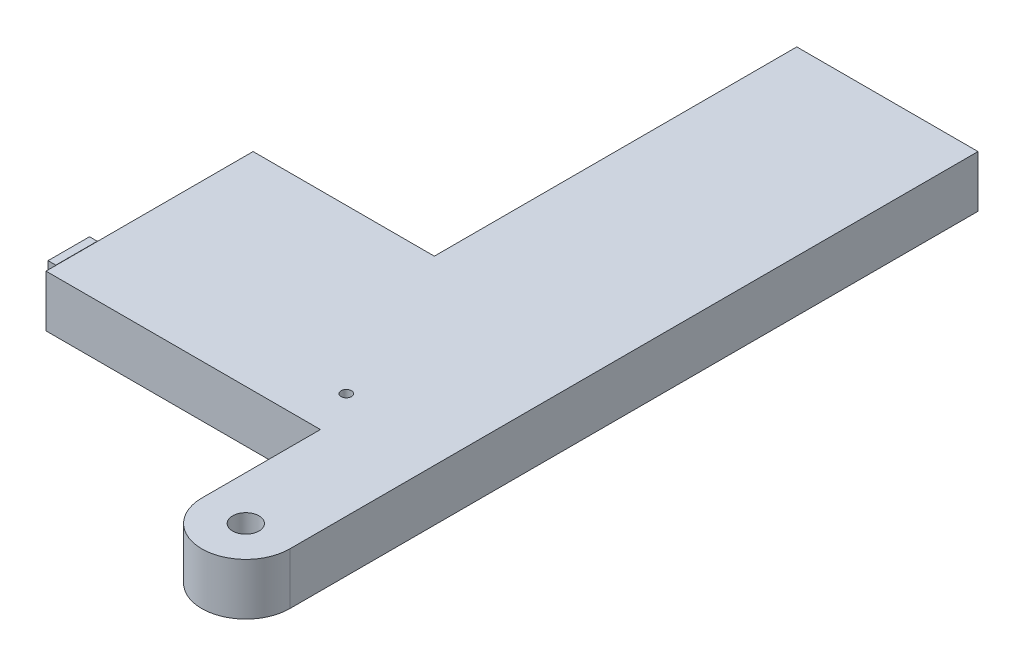
SolidWorks part; units mm, degrees
ref_plane "Front Plane" through (0, 0, 0) normal (0, 0, 1) x (1, 0, 0)
ref_plane "Top Plane" through (0, 0, 0) normal (0, 1, 0) x (1, 0, 0)
ref_plane "Right Plane" through (0, 0, 0) normal (1, 0, 0) x (0, 0, -1)
sketch "CornerrSketch1" plane through (0, 0, 0) normal (0, 1, 0) x (1, 0, 0)
  line L0 (0, 0) -> (0, 80)
  line L5 (0, 80) -> (70, 80)
  line L6 (70, 80) -> (70, 220)
  line L7 (140, 220) -> (70, 220)
  line L8 (106, -45.825) -> (106, 0)
  line L9 (0, 0) -> (106, 0)
  line L10 (140, 220) -> (140, -45.825)
  arc A0 (106, -45.825) -> (140, -45.825) centre (123, -45.825) ccw
  dimension "D5" = 34
  dimension "D4" = 80
  dimension "D3" = 70
  dimension "D1" = 220
  dimension "D2" = 45.825
  dimension "D6" = 140
extrude "CornerBoss-Extrude1" add sketch "CornerrSketch1" along normal blind 20
shell "Shell1" thickness 3 removed face at (79, 0, -61.4188)
sketch "PadSketch1" plane through (0, 17, 0) normal (0, -1, 0) x (1, 0, 0)
  line L1 (0, 0) -> (106, 0) construction
  line L2 (140, 45.825) -> (140, -220) construction
  circle A0 centre (99, -17) radius 5
  circle A1 centre (123, 45.825) radius 12
  dimension "D1" = 10
  dimension "D4" = 24
  dimension "D3" = 17
  dimension "D2" = 41
extrude "PadBoss-Extrude1" add sketch "PadSketch1" along normal blind 10
sketch "StepperShaftCut-Sketch3" plane through (0, 7, 0) normal (0, -1, 0) x (1, 0, 0)
  circle A0 centre (123, 45.825) radius 5.1
  circle A1 centre (99, -17) radius 2
  dimension "D1" = 10.2
  dimension "D2" = 4
extrude "StepperShaftCut-Extrude1" cut sketch "StepperShaftCut-Sketch3" against normal through all
sketch "ThreadedNutMountHolesSketch5" plane through (0, 7, 0) normal (0, -1, 0) x (1, 0, 0)
  circle A0 centre (123, 53.825) radius 2
  circle A1 centre (131, 45.825) radius 2
  circle A2 centre (115, 45.825) radius 2
  circle A3 centre (123, 37.825) radius 2
  dimension "D3" = 4
  dimension "D1" = 8
  dimension "D2" = 16
  dimension "D4" = 8
  dimension "D5" = 16
extrude "ThreadedNutMountHolesCut-Extrude2" cut sketch "ThreadedNutMountHolesSketch5" against normal blind 10
sketch "TopPegHoleSketch4" plane through (0, 0, -220) normal (0, 0, -1) x (-1, 0, 0)
  line L1 (-130, 14) -> (-120, 14)
  line L2 (-130, 14) -> (-130, 0)
  line L3 (-130, 0) -> (-120, 0)
  line L4 (-120, 14) -> (-120, 0)
  line L5 (-140, 0) -> (-70, 0) construction
  line L6 (-140, 20) -> (-140, 0) construction
  dimension "D2" = 10
  dimension "D3" = 14
  dimension "D1" = 10
extrude "TopPegHoleCut-Extrude2" cut sketch "TopPegHoleSketch4" against normal blind 3
sketch "BLPegSketch5" plane through (0, 0, 0) normal (-1, 0, 0) x (0, 0, 1)
  line L1 (-19.9, 13.9) -> (-10.1, 13.9)
  line L2 (-19.9, 13.9) -> (-19.9, 0)
  line L3 (-19.9, 0) -> (-10.1, 0)
  line L4 (-10.1, 13.9) -> (-10.1, 0)
  line L5 (-80, 0) -> (0, 0) construction
  line L6 (0, 20) -> (0, 0) construction
  dimension "D2" = 13.9
  dimension "D3" = 9.8
  dimension "D1" = 10.1
extrude "BLPegBoss-Extrude3" add sketch "BLPegSketch5" along normal blind 3.1
sketch "BLPegCapSketch6" plane through (-3.1, 0, 0) normal (-1, 0, 0) x (0, 0, 1)
  line L0 (-19.9, 13.9) -> (-19.9, 0) construction
  line L1 (-22.9, 17) -> (-6.9, 17)
  line L2 (-22.9, 17) -> (-22.9, 0)
  line L3 (-22.9, 0) -> (-6.9, 0)
  line L4 (-6.9, 17) -> (-6.9, 0)
  line L8 (-19.9, 0) -> (-10.1, 0) construction
  dimension "D1" = 16
  dimension "D3" = 17
  dimension "D2" = 3
extrude "BLPegCapBoss-Extrude4" add sketch "BLPegCapSketch6" along normal blind 3
sketch "BedCenterPegHoleCutSketch1" plane through (70, 0, 0) normal (-1, 0, 0) x (0, 0, 1)
  line L0 (-220, 0) -> (-80, 0) construction
  line L1 (-190, 14) -> (-180, 14)
  line L2 (-190, 14) -> (-190, 0)
  line L3 (-190, 0) -> (-180, 0)
  line L4 (-180, 14) -> (-180, 0)
  line L5 (-80, 20) -> (-80, 0) construction
  dimension "D2" = 10
  dimension "D1" = 14
  dimension "D3" = 100
extrude "BedCenterPegHoleCut-Extrude1" cut sketch "BedCenterPegHoleCutSketch1" against normal blind 3
equation "\"BedThickness\"= 20mm"
equation "\"BedToBuildPlateStandoffHolesDistanceFromLeftOrRight\"= \"BuildPlateStandoffHolesDistanceFromLeftOrRight\" + \"BedIncreasedByWidth\" / 2'Equals 17"
equation "\"BedLLongSide\"= \"BedThirdSize\" * 3'Equals 210"
equation "\"BedLShortSide\"= \"BedThirdSize\" * 2'Equals 140"
equation "\"BedLWidth\"= \"BedThirdSize\"'Equals 70"
equation "\"D4@CornerrSketch1\"=\"BedLWidth\" + \"BedIncreasedByWidth\"/2"
equation "\"BedIncreasedByWidth\"= 20mm"
equation "\"BedIncreasedByLength\"= 0mm"
equation "\"BedThirdSize\"= 70mm"
equation "\"StandardWallThickness\"= 3mm"
equation "\"D2@TopPegHoleSketch4\"=\"BedPegHoleWidth\""
equation "\"D3@TopPegHoleSketch4\"=\"BedPegHoleHeight\""
equation "\"D1@TopPegHoleCut-Extrude2\" = \"StandardWallThickness\""
equation "\"D3@BLPegSketch5\"=\"BedPegWidth\""
equation "\"D1@BLPegBoss-Extrude3\"=\"BedPegBoss\""
equation "\"D2@BLPegSketch5\"=\"BedPegHeight\""
equation "\"D2@BLPegCapSketch6\"=\"StandardWallThickness\""
equation "\"D3@BLPegCapSketch6\"=\"BedPegCapHeight\""
equation "\"D1@BLPegCapBoss-Extrude4\" = \"StandardWallThickness\""
equation "\"D3@CornerrSketch1\"=\"BedLWidth\" "
equation "\"D1@PadSketch1\" = \"BedToBuildPlateStandoffPadSize\""
equation "\"D1@PadBoss-Extrude1\"=\"LeadScrewNutPadDepth\""
equation "\"BedToBuildPlateStandoffPadSize\"= 10mm"
equation "\"BedToBuildPlateStandoffHolesDistanceFromBack\"= \"BuildPlateStandoffHolesDistanceFromBack\" + \"BedIncreasedByLength\" / 2'Equals 41"
equation "\"BuildPlateStandoffHolesDistanceFromLeftOrRight\"= 7mm"
equation "\"BuildPlateStandoffHolesDistanceFromBack\"= 41mm"
equation "\"DistanceFromBedSideToStepperHole\"= ( \"DistanceBetweenLeftToRightStepperHoles\" - \"BedWidth\" ) / 2'Equals 45.825"
equation "\"DistanceBetweenLeftToRightStepperHoles\"= \"FrontBackRailLength\" - \"StepperMountingHoleOffsetFromLeftOrRightSide\" * 2 - \"StepperMountingHoleDistance\"'Equals 461.65"
equation "\"FrontBackRailLength\"= 510mm"
equation "\"StepperMountingHoleOffsetFromLeftOrRightSide\"= \"StepperMountingHoleOffsetFromItsSide\" + \"RailThickness\""
equation "\"StepperMountingHoleDistance\"= 31mm'Spec"
equation "\"StepperMountingHoleOffsetFromItsSide\"= 5.5mm'Spec"
equation "\"RailThickness\"= .125in'Spec"
equation "\"BedWidth\"= \"BedInnerSquareWidth\" + \"BedLWidth\" * 2 + \"BedIncreasedByWidth\"'Equals 370"
equation "\"BedInnerSquareWidth\"= \"BedThirdSize\" * 3'Equals 210"
equation "\"D1@CornerrSketch1\"=\"BedLLongSide\"  + \"BedIncreasedByWidth\"/2"
equation "\"D2@CornerrSketch1\"=\"DistanceFromBedSideToStepperHole\""
equation "\"D3@PadSketch1\"=\"BedToBuildPlateStandoffHolesDistanceFromLeftOrRight\""
equation "\"D2@PadSketch1\"=\"BedToBuildPlateStandoffHolesDistanceFromBack\""
equation "\"D1@TopPegHoleSketch4\"=\"BedTopPegOffsetFromSide\""
equation "\"D1@BLPegSketch5\"=\"BedTopPegOffsetFromSide\" + .1mm"
equation "\"D6@CornerrSketch1\"=\"BedLShortSide\" + \"BedIncreasedByLength\"/2"
equation "\"LeadScrewNutPadSize\"= \"LeadScrewNutMountingHoleFlangeDiameter\" + 2mm'Equals 24"
equation "\"D4@PadSketch1\"=\"LeadScrewNutPadSize\""
equation "\"D1@StepperShaftCut-Sketch3\"=\"LeadScrewNutInnerShaftFlangeDiameter\""
equation "\"D2@StepperShaftCut-Sketch3\"=\"M3HeatInsertHoleDiameter\""
equation "\"LeadScrewNutInnerShaftFlangeDiameter\"= 10.2mm'Spec"
equation "\"LeadScrewNutMountHoleDiameter\"= \"M3HeatInsertHoleDiameter\""
equation "\"LeadScrewNutMountingHoleFlangeDiameter\"= 22mm'Spec"
equation "\"LeadScrewNutMountingHoleDistance\"= 16mm'Spec"
equation "\"D1@ThreadedNutMountHolesSketch5\"=\"LeadScrewNutMountingHoleDistance\"/2"
equation "\"D2@ThreadedNutMountHolesSketch5\"=\"LeadScrewNutMountingHoleDistance\""
equation "\"D4@ThreadedNutMountHolesSketch5\"=\"LeadScrewNutMountingHoleDistance\"/2"
equation "\"D5@ThreadedNutMountHolesSketch5\"=\"LeadScrewNutMountingHoleDistance\""
equation "\"D3@ThreadedNutMountHolesSketch5\"=\"LeadScrewNutMountHoleDiameter\""
equation "\"LeadScrewNutPadDepth\"= \"BedThickness\" / 2'Equals 10"
equation "\"D1@ThreadedNutMountHolesCut-Extrude2\"= \"LeadScrewNutPadDepth\""
equation "\"BedPegHoleWidth\"= 10mm"
equation "\"BedPegHoleHeight\"= \"BedThickness\" - \"StandardWallThickness\" * 2'Equals 14"
equation "\"BedPegWidth\"= \"BedPegHoleWidth\" - .1mm * 2'For easier assembly"
equation "\"BedPegHeight\"= \"BedPegHoleHeight\" - .1mm'For easier assembly"
equation "\"BedTopPegOffsetFromSide\"= 10mm"
equation "\"BedPegBoss\"= \"StandardWallThickness\" + .1mm'For easier assembly"
equation "\"BedPegCapHeight\"= \"BedThickness\" - \"StandardWallThickness\"'Equals 17"
equation "\"BedPegCapWidth\"= \"BedThickness\" / 2 + \"StandardWallThickness\" * 2'Equals 16"
equation "\"D1@BLPegCapSketch6\"=\"BedPegCapWidth\""
equation "\"D1@BedCenterPegHoleCutSketch1\" = \"BedPegHoleHeight\""
equation "\"D3@BedCenterPegHoleCutSketch1\" = \"BedInnerSquareWidth\" / 2 - \"BedPegHoleWidth\" / 2"
equation "\"D2@BedCenterPegHoleCutSketch1\" = \"BedPegHoleWidth\""
equation "\"D1@BedCenterPegHoleCut-Extrude1\"=\"StandardWallThickness\""
equation "\"M3HeatInsertHoleDiameter\"= 4mm'Spec"
